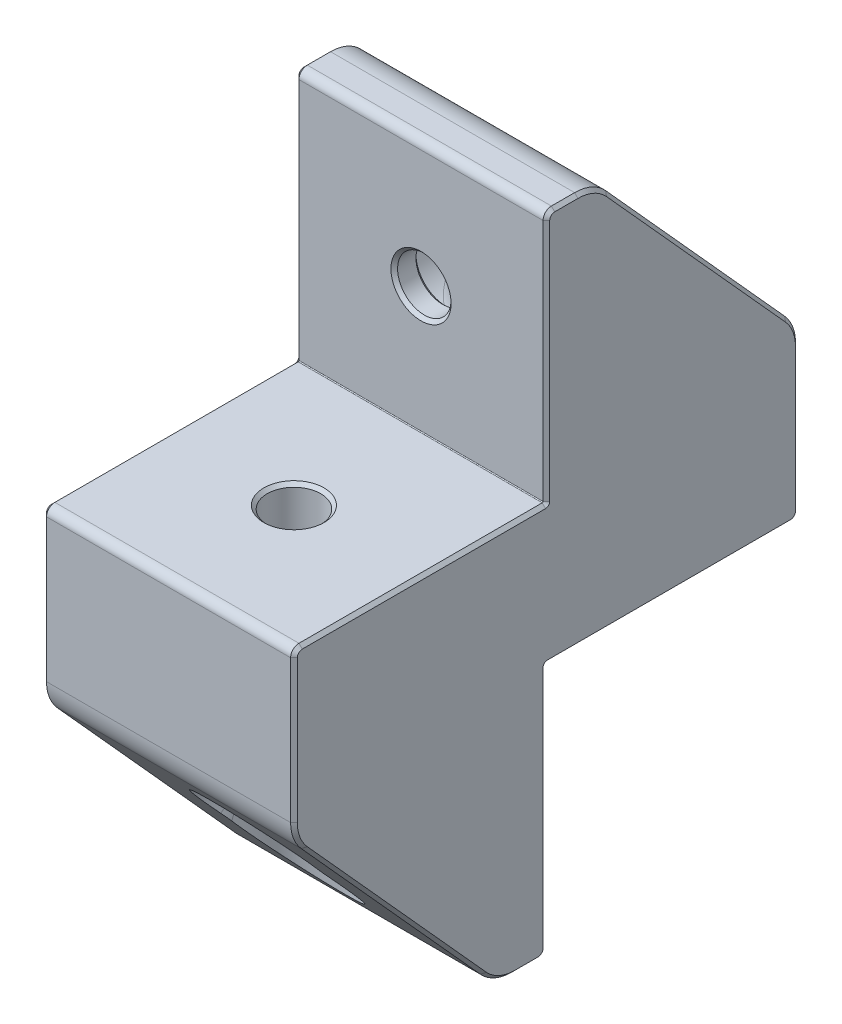
SolidWorks part; units mm, degrees
note: The reader was unsure of these and kept them because the rebuilt part matched: shared geometry of "Sketch2<3>", "Sketch2<4>", "Sketch5<3>".
ref_plane "Front Plane" through (0, 0, 0) normal (1, 0, 0) x (0, 1, 0)
ref_plane "Top Plane" through (0, 0, 0) normal (0, 0, 1) x (0, 1, 0)
ref_plane "Right Plane" through (0, 0, 0) normal (0, 1, 0) x (-1, 0, 0)
sketch "Sketch1" plane through (0, 0, 0) normal (1, 0, 0) x (0, 1, 0)
  line L0 (0, 0) -> (-30.2, 0)
  line L1 (-30.2, 0) -> (-30.2, 6)
  line L2 (-30.2, 6) -> (-3.4, 30.2)
  line L3 (-3.4, 30.2) -> (16.6, 30.2)
  line L4 (16.6, 30.2) -> (16.6, 0)
  line L5 (16.6, 0) -> (46.8, 0)
  line L6 (46.8, 0) -> (46.8, -6)
  line L7 (46.8, -6) -> (20, -30.2)
  line L8 (20, -30.2) -> (0, -30.2)
  line L9 (0, -30.2) -> (0, 0)
  point P10 (0, 0)
  point P12 (-0.6249, 30.2)
  dimension "D1" = 30.2
  dimension "D2" = 46.8
  dimension "D3" = 30.2
  dimension "D4" = 30.2
  dimension "D5" = 30.2
  dimension "D6" = 6
  dimension "D7" = 20
extrude "Boss-Extrude1" add sketch "Sketch1" along normal blind 15
sketch "Sketch2" plane through (0, 0, 0) normal (0, 0, -1) x (1, 0, 0)
  line L0 (15, 30.2) -> (0, 30.2) construction
  line L4 (0, -16.6) -> (0, -46.8)
  line L5 (15, -16.6) -> (0, -16.6)
  line L6 (15, -46.8) -> (15, -16.6)
  line L7 (0, -46.8) -> (15, -46.8)
  line L8 (0, -16.6) -> (0, -46.8)
  line L9 (15, -16.6) -> (0, -16.6)
  line L10 (15, -46.8) -> (15, -16.6)
  line L11 (0, -46.8) -> (15, -46.8)
  line L12 (0, 30.2) -> (0, 0)
  line L13 (0, 0) -> (15, 0)
  line L14 (15, 0) -> (15, 30.2)
  line L15 (15, 30.2) -> (0, 30.2)
  line L16 (0, 30.2) -> (0, 0)
  line L17 (0, 0) -> (15, 0)
  line L18 (15, 0) -> (15, 30.2)
  line L19 (15, 30.2) -> (0, 30.2)
  line L28 (0, 30.2) -> (0, 0) construction
  circle A0 centre (0, 15.1) radius 3.2
  circle A1 centre (0, -31.7) radius 3.2
  circle A2 centre (0, 15.1) radius 6
  circle A3 centre (0, -31.7) radius 6
  point P6 (0, 15.2)
  point P55 (0, -31.8)
  line M9 (0, 30.2) -> (0, 0)
  dimension "D5" = 6.4
  dimension "D6" = 12
  dimension "D3" = 15
  dimension "D4" = 15
  dimension "D1" = 0
  dimension "D2" = 0
extrude "Cut-Extrude1" cut sketch "Sketch2" against normal through all both and the other way through all contours L16 A0 | L8 A1
extrude "Cut-Extrude2" cut sketch "Sketch2<3>" along normal through all from offset 3 contours L8 A3 A1
sketch "Sketch2<3>" plane through (0, 0, 0) normal (0, 0, -1) x (1, 0, 0) same geometry as "Sketch2"
extrude "Cut-Extrude3" cut sketch "Sketch2<4>" against normal through all from offset 3 contours A2 L16 A0 M9 offset against normal yes
sketch "Sketch2<4>" plane through (0, 0, 0) normal (0, 0, -1) x (1, 0, 0) same geometry as "Sketch2"
sketch "Sketch5" plane through (0, 16.6, 0) normal (0, 1, 0) x (-1, 0, 0)
  line L0 (0, 0) -> (0, 30.2) construction
  line L1 (0, 0) -> (0, -30.2) construction
  line L2 (0, 0) -> (0, -30.2)
  line L3 (0, 0) -> (0, 30.2)
  circle A0 centre (0, 15.2) radius 3.2
  circle A1 centre (0, 15.2) radius 6
  circle A2 centre (0, -15.2) radius 3.2
  line M3 (0, 0) -> (0, 30.2)
  dimension "D1" = 15
  dimension "D3" = 6.4
  dimension "D4" = 12
  dimension "D2" = 15
extrude "Cut-Extrude4" cut sketch "Sketch5" against normal through all both and the other way through all contours L3 A0 | L2 A2
extrude "Cut-Extrude5" cut sketch "Sketch5<3>" against normal through all from offset 19 contours A1 L3 A0 M3 offset against normal yes
sketch "Sketch5<3>" plane through (0, 16.6, 0) normal (0, 1, 0) x (-1, 0, 0) same geometry as "Sketch5"
sketch "Sketch6" plane through (0, 0, 0) normal (0, -1, 0) x (1, 0, 0)
  line L5 (0, 0) -> (0, -12)
  line L6 (0, -18.4) -> (0, -30.2)
  line L7 (0, -30.2) -> (15, -30.2)
  line L8 (15, -30.2) -> (15, 0)
  line L9 (15, 0) -> (0, 0)
  line L10 (0, 0) -> (0, -12)
  line L11 (0, -18.4) -> (0, -30.2)
  line L12 (0, -30.2) -> (15, -30.2)
  line L13 (15, -30.2) -> (15, 0)
  line L14 (15, 0) -> (0, 0)
  circle A0 centre (0, -15.2) radius 6
  arc A1 (0, -18.4) -> (0, -12) centre (0, -15.2) ccw
  arc A2 (0, -18.4) -> (0, -12) centre (0, -15.2) ccw
  circle A3 centre (0, 15.2) radius 6 construction
  arc M9 (0, -12) -> (0, -18.4) centre (0, -15.2) cw
  line M10 (0, -18.4) -> (0, -30.2)
  dimension "D1" = 0
extrude "Cut-Extrude6" cut sketch "Sketch6" against normal through all from offset 19 contours A0 L10 M10 M9 offset against normal yes
fillet "Fillet1" radius 5 4 edges at (7.5, -30.2, 6) (7.5, 46.8, -6) (7.5, 20, -30.2) (7.5, -3.4, 30.2)
fillet "Fillet2" radius 1 4 edges at (7.5, 16.6, 30.2) (7.5, 0, -30.2) (7.5, 46.8, 0) (7.5, -30.2, 0)
fillet "Fillet3" radius 0.1 2 edges at (7.5, 16.6, 0) (7.5, 0, 0)
chamfer "Chamfer1" distance 0.4 angle 45 32 edges at (15, 46.3692, -5.8086) (15, 33.2892, -18.2) (15, 19.8718, -29.8666) (15, 9.5383, -30.2) (15, 0.2929, -29.9071) (15, 0, -14.65) (15, -0.0293, -0.0293) (15, -14.65, 0) (15, -29.9071, 0.2929) (15, -30.2, 2.3891) (15, -29.7692, 5.8086) (15, -16.6892, 18.2) (15, -3.2718, 29.8666) (15, 7.0617, 30.2) (15, 16.3071, 29.9071) (15, 16.6, 14.65) (15, 16.6293, 0.0293) (15, 31.25, 0) (15, 46.5071, -0.2929) (15, 46.8, -2.3891) (3.2, -15.1, 0) (3.2, -15.1, 3) (3.2, 31.7, 0) (3.2, 31.7, -3) (3.2, 16.6, 15.2) (3.2, -2.4, 15.2) (3.2, 0, -15.2) (3.2, 19, -15.2) (6, -15.1, 3) (6, 19, -15.2) (6, 31.7, -3) (6, -2.4, 15.2)
fillet "Fillet4" radius 5 4 edges at (4.2426, -10.8574, 10.9574) (4.2426, 27.4574, -10.9574) (5.881, -16.2889, 16.3889) (5.881, 32.8889, -16.3889)
fillet "Fillet5" radius 2 4 edges at (4.2426, 35.9426, -10.9574) (4.2426, 27.4574, -19.4426) (4.2426, -19.3426, 10.9574) (4.2426, -10.8574, 19.4426)
mirror "Mirror1" about plane through (0, 0, 0) normal (1, 0, 0) of bodies 107
